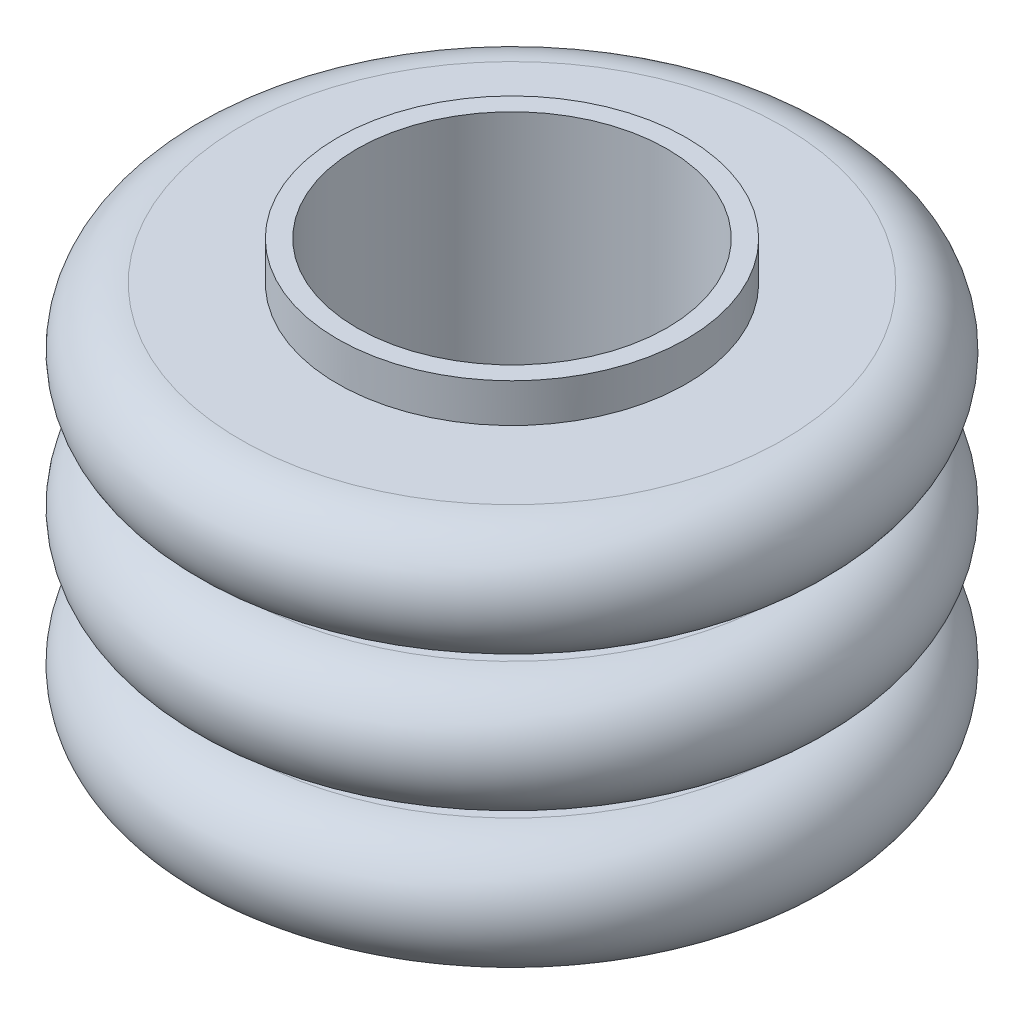
SolidWorks part; units mm, degrees
ref_plane "Front Plane" through (0, 0, 0) normal (0, 0, 1) x (1, 0, 0)
ref_plane "Top Plane" through (0, 0, 0) normal (0, 1, 0) x (1, 0, 0)
ref_plane "Right Plane" through (0, 0, 0) normal (1, 0, 0) x (0, 0, -1)
sketch "Sketch1" plane through (0, 0, 0) normal (0, 1, 0) x (1, 0, 0)
  circle A0 centre (0, 0) radius 5.08
  circle A1 centre (0, 0) radius 5.715
  dimension "D1" = 10.16
  dimension "D2" = 0.635
extrude "Boss-Extrude1" add sketch "Sketch1" along normal blind 13.97
sketch "Sketch2" plane through (0, 0, 0) normal (0, -1, 0) x (1, 0, 0)
  circle A0 centre (0, 0) radius 5.715 construction
  circle A1 centre (0, 0) radius 5.715
  circle A2 centre (0, 0) radius 10.795
  circle A3 centre (0, 0) radius 5.08 construction
  circle A4 centre (0, 0) radius 5.08
  circle M1 centre (0, 0) radius 5.715
  dimension "D1" = 21.59
extrude "Boss-Extrude2" add sketch "Sketch2" against normal blind 3.81 contours A2 M1 region at (-10.4897, 0, 0)
ref_axis "Axis1" through (0, 13.97, 0) along (0, -1, 0)
pattern_linear "LPattern1" count 3 spacing 4.445 along (0, 1, 0) of "Boss-Extrude2"
fillet "Fillet1" 2 edges at (0, 0, -10.795) (0, 3.81, -10.795) type full round first side face at (0, 0, 5.08) second side face at (0, 3.81, -5.715) middle face at (0, 3.81, -10.795)
fillet "Fillet2" 2 edges at (0, 4.445, -10.795) (0, 8.255, -10.795) type full round first side face at (0, 4.445, -5.715) second side face at (0, 8.255, -5.715) middle face at (0, 8.255, -10.795)
fillet "Fillet3" 2 edges at (0, 8.89, -10.795) (0, 12.7, -10.795) type full round first side face at (0, 8.89, -5.715) second side face at (0, 12.7, -5.715) middle face at (0, 12.7, -10.795)
